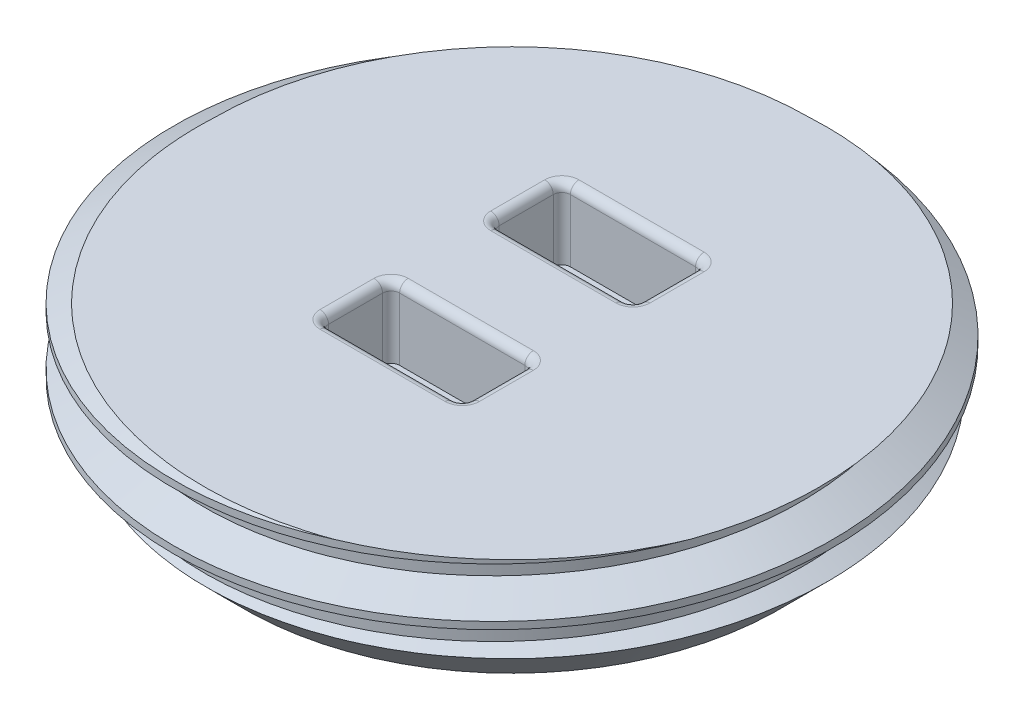
SolidWorks part; units mm, degrees
note: The reader was unsure of these and kept them because the rebuilt part matched: shared geometry of "Sketch9<2>".
ref_plane "Front Plane" through (0, 0, 0) normal (0, 0, 1) x (1, 0, 0)
ref_plane "Top Plane" through (0, 0, 0) normal (0, 1, 0) x (1, 0, 0)
ref_plane "Right Plane" through (0, 0, 0) normal (1, 0, 0) x (0, 0, -1)
sketch "Sketch1" plane through (0, 0, 0) normal (0, 1, 0) x (1, 0, 0)
  circle A0 centre (0, 0) radius 13.335
  dimension "D1" = 26.67
extrude "Boss-Extrude1" add sketch "Sketch1" along normal blind 6.35
sketch "Sketch5" plane through (0, 0, 0) normal (0, 0, 1) x (1, 0, 0)
  line L0 (0.762, 7.1618) -> (-0.762, 7.1618)
  line L1 (-0.762, 7.1618) -> (0, 5.842)
  line L2 (0, 5.842) -> (0.762, 7.1618)
  point P2 (0, 0)
  point P4 (0, 5.8551)
  point P6 (0, 7.1618)
  point P8 (-0.7845, 7.0739)
  point P9 (0, 0)
  dimension "D1" = 5.842
  dimension "D2" = 1.524
extrude "Cut-Extrude2" [suppressed] cut sketch "Sketch5" against normal through all
chamfer "Chamfer1" [suppressed] distance 2.032 angle 45
thread "Thread1" pitch 2.54 method extrude profile "Thread Profile1" start angle 0, offset 2.54, length 0, pitch 2.54, diameter 26.67
ref_plane "Plane1" through (-13.335, 8.89, 0) normal (0, 0, 1) x (-1, 0, 0)
sketch "Thread Profile1" plane through (-13.335, 8.89, 0) normal (0, 0, 1) x (-1, 0, 0)
  line L0 (0, 0) -> (0, 2.54) construction
  line L1 (0, 0) -> (1.3748, 0.7937)
  line L2 (1.3748, 0.7937) -> (1.3748, 1.1112)
  line L3 (1.3748, 1.1112) -> (0, 1.905)
  line L4 (1.3748, 0.9525) -> (0, 0.9525) construction
  line L11 (0, 0) -> (0, 1.905)
  point P2 (0, 0)
  dimension "Pitch" = 2.54
  dimension "Profile_Angle" = 60
  dimension "Profile_Land" = 0.3175
  dimension "Profile_Height" = 1.3748
sketch "Sketch4" plane through (0, 6.35, 0) normal (0, 1, 0) x (1, 0, 0)
  line L0 (0, 0) -> (-5.9339, 0) construction
  line L1 (3.175, 2.2225) -> (-3.175, 2.2225)
  line L2 (3.175, 2.2225) -> (3.175, 5.3975)
  line L3 (3.175, 5.3975) -> (-3.175, 5.3975)
  line L4 (-3.175, 2.2225) -> (-3.175, 5.3975)
  line L5 (3.175, 2.2225) -> (-3.175, 5.3975) construction
  line L6 (3.175, 5.3975) -> (-3.175, 2.2225) construction
  line L7 (3.175, -5.3975) -> (-3.175, -5.3975)
  line L8 (-3.175, -2.2225) -> (-3.175, -5.3975)
  line L9 (3.175, -2.2225) -> (-3.175, -2.2225)
  line L10 (3.175, -2.2225) -> (3.175, -5.3975)
  point P0 (0, 3.81)
  point P6 (0, 0)
  dimension "D1" = 3.175
  dimension "D2" = 6.35
  dimension "D3" = 3.81
extrude "Cut-Extrude1" cut sketch "Sketch4" against normal blind 3.175
fillet "Fillet1" radius 0.381 16 edges at (0, 6.35, 2.2225) (3.175, 6.35, -3.81) (0, 6.35, -5.3975) (-3.175, 6.35, -3.81) (0, 6.35, -2.2225) (3.175, 6.35, 3.81) (-3.175, 6.35, 3.81) (0, 6.35, 5.3975) (-3.175, 4.7625, -2.2225) (-3.175, 4.7625, -5.3975) (3.175, 4.7625, -5.3975) (3.175, 4.7625, -2.2225) (3.175, 4.7625, 5.3975) (3.175, 4.7625, 2.2225) (-3.175, 4.7625, 2.2225) (-3.175, 4.7625, 5.3975)
sketch "Sketch9" plane through (0, 6.35, 0) normal (0, 1, 0) x (1, 0, 0)
  circle A0 centre (0, 0) radius 24.6687
extrude "Cut-Extrude3" cut sketch "Sketch9" along normal through all
extrude "Cut-Extrude4" cut sketch "Sketch9<2>" against normal through all from surface at -6.35 starting at face at (6.6675, 0, 6.6675)
sketch "Sketch9<2>" plane through (0, 6.35, 0) normal (0, 1, 0) x (1, 0, 0) same geometry as "Sketch9"
ref_axis "Axis1" through (0, -1.2383, 0) along (0, 1, 0)
sketch "Sketch10" plane through (0, 0, 0) normal (1, 0, 0) x (0, 0, -1)
  line L0 (-16.256, 2.6525) -> (-14.5905, 2.6525)
  line L1 (-14.5905, 2.6525) -> (-11.938, 0)
  line L2 (-11.938, 0) -> (-16.256, 0)
  line L3 (-16.256, 0) -> (-16.256, 2.6525)
  line L4 (13.335, 0) -> (-13.335, 0) construction
  point P2 (-11.938, 0)
  point P8 (-14.5905, 2.6525)
  dimension "D1" = 16.256
  dimension "D2" = 45
  dimension "D3" = 4.318
revolve "Cut-Revolve1" cut sketch "Sketch10" angle 360 about axis through (0, -1.2383, 0) along (0, 1, 0)
